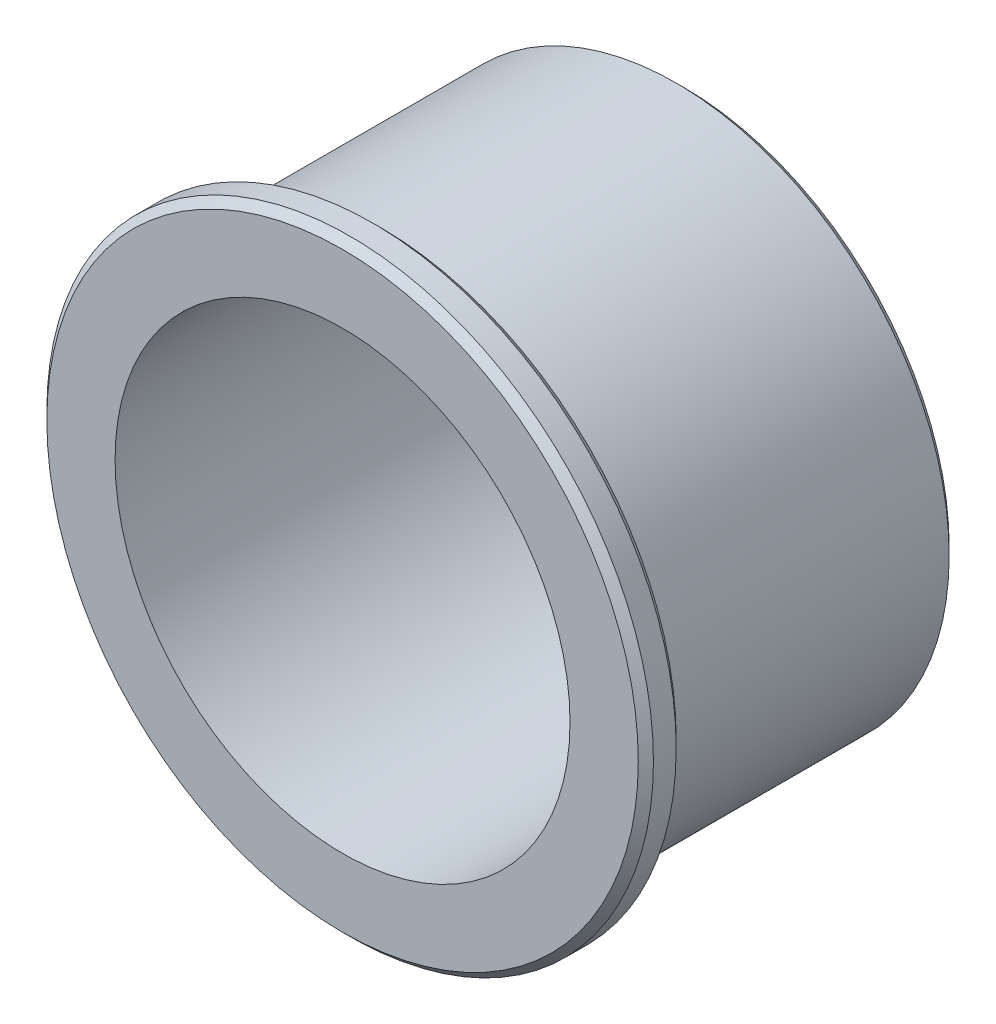
SolidWorks part; units mm, degrees
note: '?' marks a value the reader was unsure of.
ref_plane "Front" through (0, 0, 0) normal (0, 0, 1) x (1, 0, 0)
ref_plane "Top" through (0, 0, 0) normal (0, 1, 0) x (1, 0, 0)
ref_plane "Right" through (0, 0, 0) normal (1, 0, 0) x (0, 0, -1)
ref_axis "Axis1" through (-84.4107, 0, 0) along (1, 0, 0)?
ref_axis "Axis2" through (0, 64.3378, 0) along (0, -1, 0)?
ref_axis "Axis3" through (0, 0, -102.329) along (0, 0, 1)?
sketch "Sketch1" plane through (0, 0, 0) normal (1, 0, 0) x (0, 0, -1)
  line L0 (-38.9835, 0) -> (32.3574, 0) construction
  line L1 (0, 15) -> (0, 20)
  line L2 (0, 20) -> (2.5, 20)
  line L3 (2.5, 20) -> (2.5, 18)
  line L4 (2.5, 18) -> (22.5, 18)
  line L5 (22.5, 18) -> (22.5, 15)
  line L6 (22.5, 15) -> (0, 15)
  dimension "D1" = 15
  dimension "D2" = 20
  dimension "D3" = 18
  dimension "D4" = 20
  dimension "D5" = 22.5
revolve "Revolve1" add sketch "Sketch1" angle 360 about L0
fillet "Fillet1" radius 0.5
chamfer "Chamfer1" distance 0.5 angle 45
